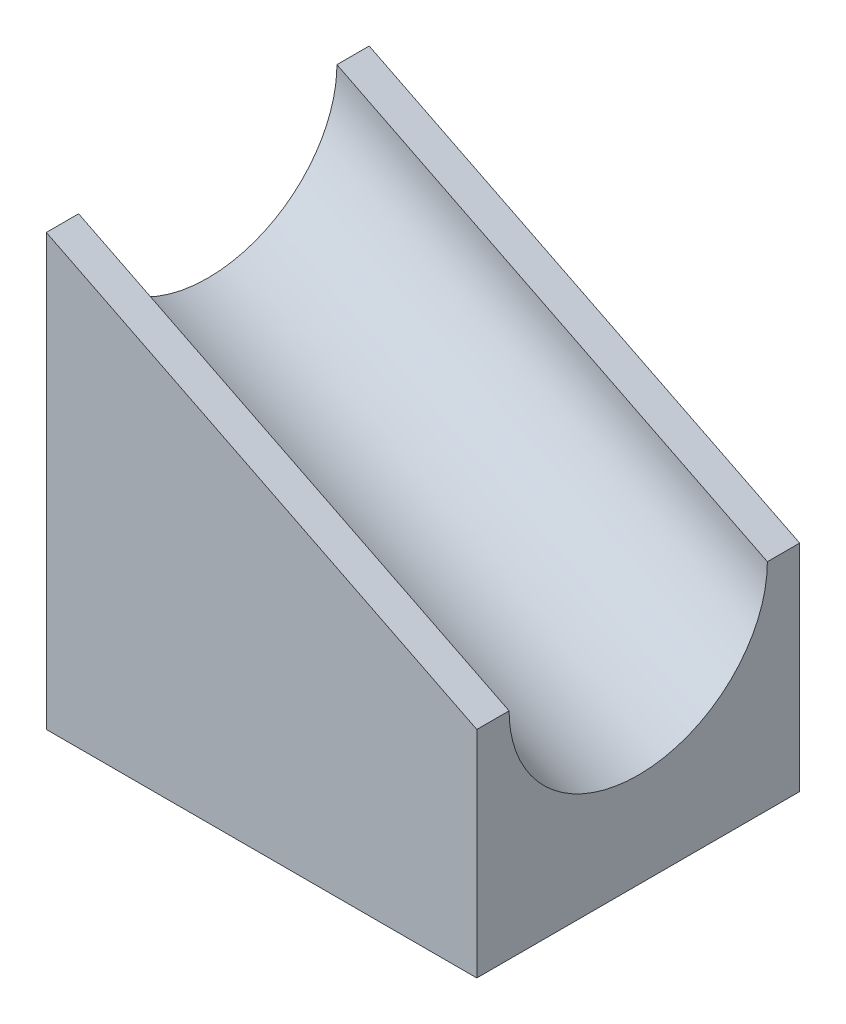
SolidWorks part; units mm, degrees
ref_plane "Front Plane" through (0, 0, 0) normal (0, 0, 1) x (1, 0, 0)
ref_plane "Top Plane" through (0, 0, 0) normal (0, 1, 0) x (1, 0, 0)
ref_plane "Right Plane" through (0, 0, 0) normal (1, 0, 0) x (0, 0, -1)
sketch "Sketch1" plane through (0, 0, 0) normal (0, 0, 1) x (1, 0, 0)
  line L0 (-12.7, 12.7) -> (12.7, 0)
  line L1 (-12.7, -12.7) -> (12.7, -12.7)
  line L2 (-12.7, -12.7) -> (-12.7, 12.7)
  line L4 (12.7, -12.7) -> (12.7, 0)
  point P0 (0, 0)
  point P1 (-12.7, 0)
  point P6 (0, -12.7)
  dimension "D1" = 25.4
  dimension "D2" = 25.4
  dimension "D3" = 12.7
extrude "Boss-Extrude1" add sketch "Sketch1" along normal blind 19.05
ref_plane "Plane1" through (-15.24, 7.62, 0) normal (-0.8944, 0.4472, 0) x (0, 0, -1)
sketch "Sketch3" plane through (-15.24, 7.62, 0) normal (-0.8944, 0.4472, 0) x (0, 0, -1)
  line L0 (-19.05, -5.6796) -> (0, -5.6796) construction
  ellipse E0 centre (-9.525, -5.6796) end of major axis (-1.905, -5.6796) minor radius 6.35
  point P1 (0, -5.6796)
  point P7 (-2.3052, -5.6796)
  dimension "D1" = 7.62
  dimension "D2" = 6.35
extrude "Cut-Extrude1" cut sketch "Sketch3" against normal through all
